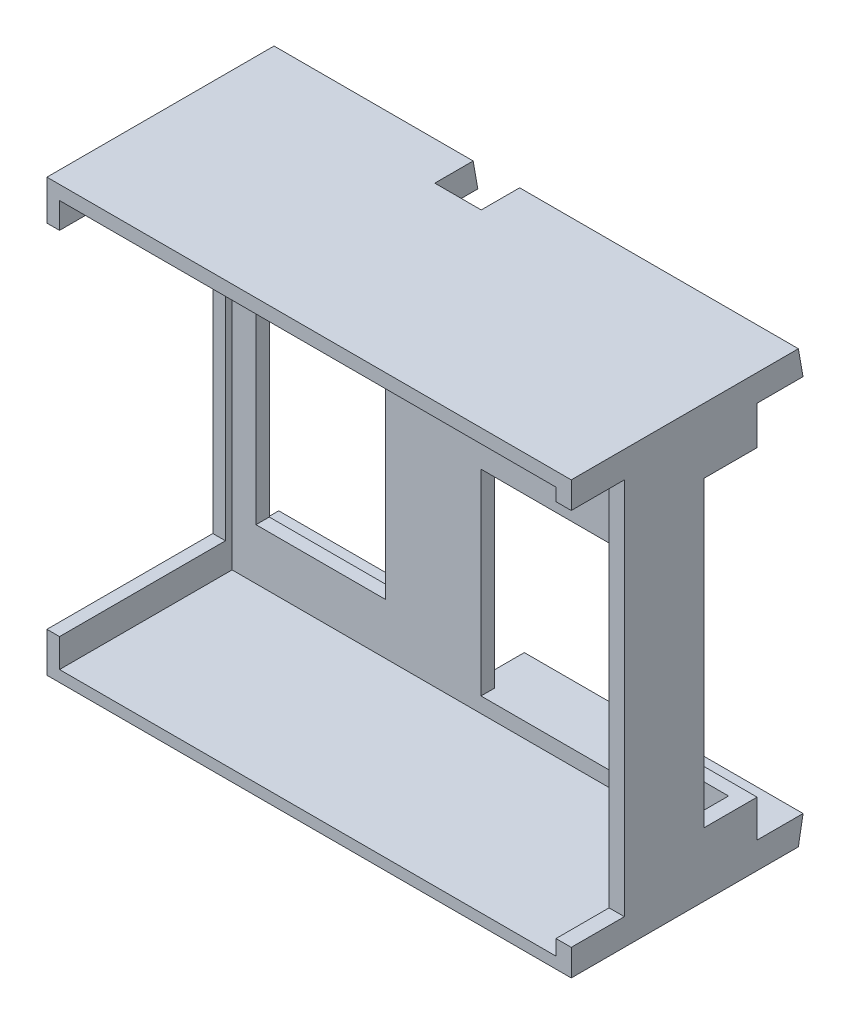
SolidWorks part; units mm, degrees
ref_plane "Plan de face" through (0, 0, 0) normal (0, 0, 1) x (1, 0, 0)
ref_plane "Plan de dessus" through (0, 0, 0) normal (0, 1, 0) x (1, 0, 0)
ref_plane "Plan de droite" through (0, 0, 0) normal (1, 0, 0) x (0, 0, -1)
sketch "Esquisse1" plane through (0, 0, 0) normal (0, 0, 1) x (1, 0, 0)
  line L1 (0, 0) -> (39.5, 0)
  line L2 (0, 0) -> (0, 32.5)
  line L3 (0, 32.5) -> (39.5, 32.5)
  line L4 (39.5, 0) -> (39.5, 32.5)
  dimension "D1" = 39.5
  dimension "D2" = 32.5
extrude "Boss.-Extru.1" add sketch "Esquisse1" along normal blind 14
sketch "Esquisse2" plane through (0, 0, 14) normal (0, 0, 1) x (1, 0, 0)
  line L1 (0.95, 0.85) -> (38.35, 0.85)
  line L2 (0.95, 0.85) -> (0.95, 31.45)
  line L3 (0.95, 31.45) -> (38.35, 31.45)
  line L4 (38.35, 0.85) -> (38.35, 31.45)
extrude "Enlèv. mat.-Extru.1" cut sketch "Esquisse2" against normal blind 13
sketch "Esquisse3" plane through (39.5, 0, 0) normal (1, 0, 0) x (0, 0, -1)
  line L1 (-14, 30.5) -> (-10, 30.5)
  line L2 (-14, 30.5) -> (-14, 2)
  line L3 (-14, 2) -> (-10, 2)
  line L4 (-10, 30.5) -> (-10, 2)
extrude "Enlèv. mat.-Extru.2" cut sketch "Esquisse3" against normal blind 5
sketch "Esquisse4" plane through (0, 0, 0) normal (-1, 0, 0) x (0, 0, 1)
  line L0 (14, 32.5) -> (0, 32.5) construction
  line L1 (1.5, 29.5) -> (14, 29.5)
  line L2 (1.5, 29.5) -> (1.5, 3)
  line L3 (1.5, 3) -> (14, 3)
  line L4 (14, 29.5) -> (14, 3)
  line L5 (14, 0) -> (0, 0) construction
  line L7 (0, 32.5) -> (0, 0) construction
  dimension "D1" = 3
  dimension "D2" = 3
  dimension "D3" = 1.5
extrude "Enlèv. mat.-Extru.3" cut sketch "Esquisse4" against normal blind 5
sketch "Esquisse6" plane through (0, 0, 1) normal (0, 0, 1) x (1, 0, 0)
  line L0 (39.5, 2) -> (39.5, 30.5) construction
  line L1 (34.5, 2) -> (19.7, 2)
  line L2 (34.5, 2) -> (34.5, 16.8)
  line L3 (34.5, 16.8) -> (19.7, 16.8)
  line L4 (19.7, 2) -> (19.7, 16.8)
  line L5 (0, 0) -> (39.5, 0) construction
  dimension "D1" = 5
  dimension "D2" = 2
  dimension "D3" = 14.8
  dimension "D4" = 14.8
extrude "Enlèv. mat.-Extru.5" cut sketch "Esquisse6" against normal through all
sketch "Esquisse7" plane through (0, 0, 1) normal (0, 0, 1) x (1, 0, 0)
  line L0 (0, 0) -> (39.5, 0) construction
  line L1 (2.75, 4.7) -> (12.5, 4.7)
  line L2 (2.75, 4.7) -> (2.75, 27.8)
  line L3 (2.75, 27.8) -> (12.5, 27.8)
  line L4 (12.5, 4.7) -> (12.5, 27.8)
  line L5 (39.5, 32.5) -> (0, 32.5) construction
  dimension "D1" = 4.7
  dimension "D2" = 4.7
extrude "Enlèv. mat.-Extru.6" cut sketch "Esquisse7" against normal through all
sketch "Esquisse8" plane through (0, 0, 0) normal (0, 0, -1) x (-1, 0, 0)
  line L1 (-35.5, 27.6) -> (-39.5, 27.6)
  line L2 (-35.5, 27.6) -> (-35.5, 4.8)
  line L3 (-35.5, 4.8) -> (-39.5, 4.8)
  line L4 (-39.5, 27.6) -> (-39.5, 4.8)
extrude "Boss.-Extru.3" add sketch "Esquisse8" against normal blind 1
extrude "Enlèv. mat.-Extru.7" cut sketch "Esquisse8<2>" against normal blind 1
sketch "Esquisse8<2>" plane through (0, 0, 0) normal (0, 0, -1) x (-1, 0, 0) same geometry as "Esquisse8"
sketch "Esquisse9" plane through (39.5, 0, 0) normal (1, 0, 0) x (0, 0, -1)
  line L1 (-1, 27.6) -> (-4, 27.6)
  line L2 (-1, 27.6) -> (-1, 4.8)
  line L3 (-1, 4.8) -> (-4, 4.8)
  line L4 (-4, 27.6) -> (-4, 4.8)
extrude "Enlèv. mat.-Extru.9" cut sketch "Esquisse9" against normal blind 1.2
sketch "Esquisse12" plane through (0, 32.5, 0) normal (0, 1, 0) x (1, 0, 0)
  line L0 (0, 0) -> (-0.0014, 12)
  line L1 (-0.0014, 12) -> (39.5, 10)
  line L2 (39.5, 10) -> (39.5, 0)
  line L3 (39.5, 0) -> (0, 0)
  dimension "D2" = 12
extrude "Boss.-Extru.6" add sketch "Esquisse12" against normal blind 2
sketch "Esquisse13" plane through (0, 0, 0) normal (0, -1, 0) x (1, 0, 0)
  line L0 (39.5, 0) -> (39.5, -10)
  line L1 (39.5, -10) -> (0, -12)
  line L2 (0, -12) -> (0, 0)
  line L3 (0, 0) -> (39.5, 0)
extrude "Boss.-Extru.7" add sketch "Esquisse13" against normal blind 2
sketch "Esquisse14" plane through (0, 0, 0) normal (0, -1, 0) x (-1, 0, 0)
  line L0 (0, -14) -> (0, 12) construction
  line L1 (0.5, 3.4641) -> (-39.5, 3.4641)
  line L2 (0.5, 3.4641) -> (0.5, 12.866)
  line L3 (0.5, 12.866) -> (-39.5, 12.866)
  line L4 (-39.5, 3.4641) -> (-39.5, 12.866)
  line L5 (-39.5, -14) -> (-39.5, 10) construction
  point P4 (-5.733, 0.3663)
  point P9 (0, 0)
  dimension "D1" = 0.5
  dimension "D2" = 0
  dimension "D3" = 1
  dimension "D4" = 3.5
extrude "Enlèv. mat.-Extru.10" cut sketch "Esquisse14" against normal through all
sketch "Esquisse15" plane through (0, 0, 0) normal (0, -1, 0) x (-1, 0, 0)
  line L0 (0, -14) -> (0, 3.4641) construction
  line L1 (-15, 0.2181) -> (-18.5, 0.2181)
  line L2 (-15, 0.2181) -> (-15, 4.2181)
  line L3 (-15, 4.2181) -> (-18.5, 4.2181)
  line L4 (-18.5, 0.2181) -> (-18.5, 4.2181)
  line L5 (-39.5, -14) -> (-39.5, 3.4641) construction
  point P4 (-9.1477, -2.094)
  point P9 (-15, 2.2181)
  dimension "D1" = 15
  dimension "D2" = 3.5
  dimension "D3" = 21
  dimension "D4" = 2
extrude "Enlèv. mat.-Extru.11" cut sketch "Esquisse15" against normal through all
chamfer "Chanfrein1" distance 2 angle 10 4 edges at (7.5, 0, -3.4641) (29, 0, -3.4641) (7.4998, 32.5, -3.4641) (29, 32.5, -3.4641) first distance on face at (7.5, 1, -3.4641) first distance on face at (29, 1, -3.4641) first distance on face at (7.4998, 31.5, -3.4641) first distance on face at (29, 31.5, -3.4641)
